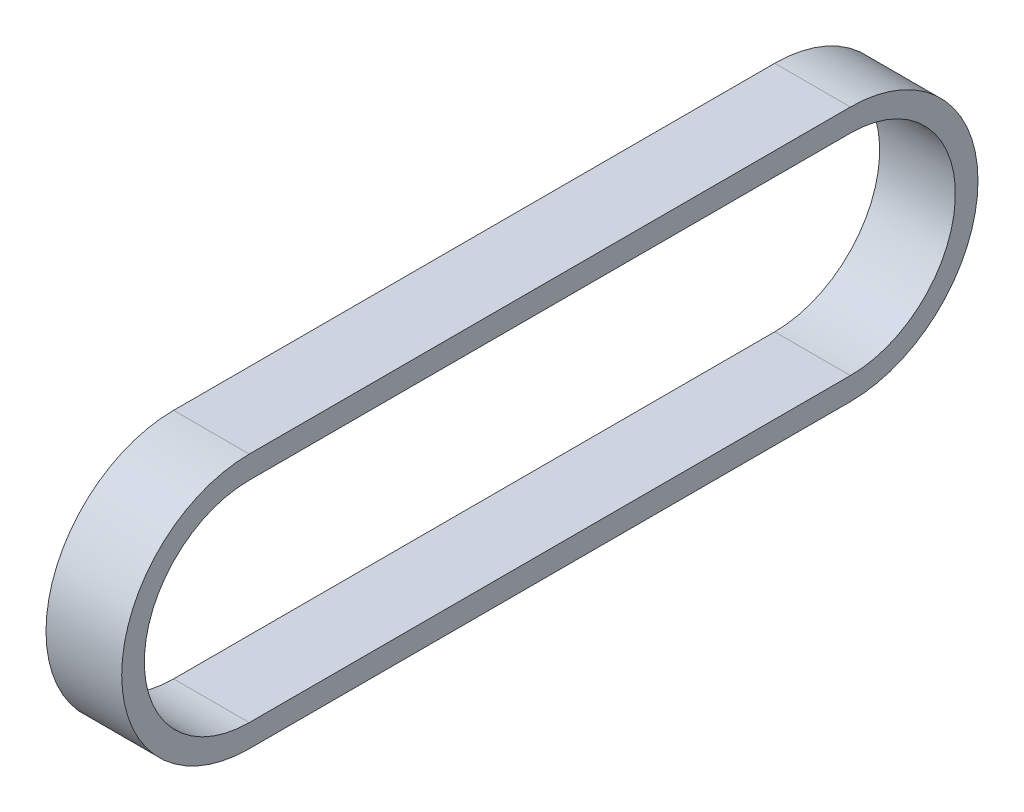
SolidWorks part; units mm, degrees
ref_plane "Front" through (0, 0, 0) normal (0, 0, 1) x (1, 0, 0)
ref_plane "Top" through (0, 0, 0) normal (0, 1, 0) x (1, 0, 0)
ref_plane "Right" through (0, 0, 0) normal (1, 0, 0) x (0, 0, -1)
sketch "Sketch1" plane through (0, 0, 0) normal (1, 0, 0) x (0, 0, -1)
  line L0 (-33.7439, 0) -> (33.7439, 0) construction
  line L1 (-33.7439, 14.3256) -> (33.7439, 14.3256)
  line L2 (-33.7439, -14.3256) -> (33.7439, -14.3256)
  arc A0 (-33.7439, 14.3256) -> (-33.7439, -14.3256) centre (-33.7439, 0) ccw
  arc A1 (33.7439, -14.3256) -> (33.7439, 14.3256) centre (33.7439, 0) ccw
  point P2 (0, 0)
  dimension "D2" = 28.6512
  dimension "D1" = 67.4878
extrude "Extrude-Thin1" add sketch "Sketch1" along normal blind 8.5 thin thin type one direction reverse wall 2.54
